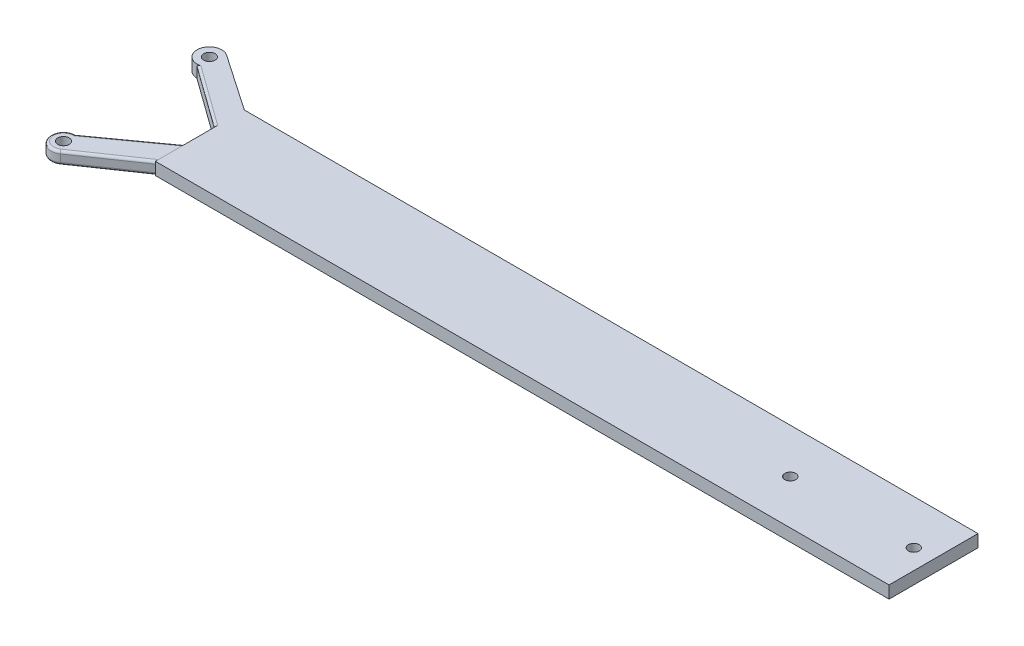
SolidWorks part; units mm, degrees
ref_plane "Płaszczyzna przednia" through (0, 0, 0) normal (0, 0, 1) x (1, 0, 0)
ref_plane "Płaszczyzna górna" through (0, 0, 0) normal (0, 1, 0) x (1, 0, 0)
ref_plane "Płaszczyzna prawa" through (0, 0, 0) normal (1, 0, 0) x (0, 0, -1)
sketch "Szkic1" plane through (0, -0.6011, 0) normal (0, -1, 0) x (1, 0, 0)
  line L11 (-159.4499, 53.1337) -> (-159.4499, 35.1337)
  line L14 (-10.9498, 35.1337) -> (-159.4499, 35.1337)
  line L15 (-10.9498, 35.1337) -> (-10.9498, 53.1337)
  line L16 (-10.9498, 53.1337) -> (-159.4499, 53.1337)
  circle A0 centre (-14.9498, 44.1337) radius 1.1 construction
  circle A1 centre (-39.9499, 44.1337) radius 1.1 construction
  circle A2 centre (-14.9498, 44.1337) radius 1.1
  circle A3 centre (-39.9499, 44.1337) radius 1.1
  dimension "D1" = 18
  dimension "D2" = 9
  dimension "D3" = 9
  dimension "D4" = 4
  dimension "D5" = 119.5
  dimension "D6" = 25.0001
extrude "Dodanie-wyciągnięcie1" add sketch "Szkic1" along normal blind 2.5
sketch "Szkic3" plane through (0, -3.1011, 0) normal (0, -1, 0) x (1, 0, 0)
  line L2 (-169.9003, 58.1452) -> (-170.1612, 57.6835)
  line L3 (-169.9187, 28.5503) -> (-170.1612, 28.0835)
  line L4 (-172.3266, 56.4033) -> (-159.4499, 47.1337)
  line L5 (-159.4499, 53.1337) -> (-159.4499, 35.1337) construction
  line L6 (-170.8688, 60.9652) -> (-159.4499, 53.1337)
  line L7 (-159.4499, 53.1337) -> (-159.4499, 47.1337)
  line L8 (-172.3266, 31.8636) -> (-159.4499, 41.1337)
  line L9 (-170.8687, 27.3018) -> (-159.4499, 35.1337)
  circle A2 centre (-172.283, 29.3637) radius 1.15
  circle A3 centre (-172.283, 58.9032) radius 1.15
  circle A4 centre (-172.283, 29.3637) radius 2.5003
  circle A5 centre (-172.283, 58.9032) radius 2.5003
  line M3 (-159.4499, 53.1337) -> (-159.4499, 35.1337)
  dimension "D1" = 6
  dimension "D2" = 6
extrude "Dodanie-wyciągnięcie2" add sketch "Szkic3" against normal blind 2.5 separate body contours A4 L9 L8 M3 | A5 L4 L6 M3 | A5 A3 | A4 A2 region at (-164.9277, -3.1011, 53.897) region at (-164.9277, -3.1011, 34.3701) region at (-174.5972, -3.1011, 59.6428) region at (-170.58, -3.1011, 31.0966)
sketch "Szkic8" plane through (0, -3.1011, 0) normal (0, -1, 0) x (1, 0, 0)
  line L1 (-159.4499, 47.1337) -> (-44.9494, 47.1337)
  line L2 (-159.4499, 47.1337) -> (-159.4499, 40.8642)
  line L3 (-159.4499, 40.8642) -> (-44.9494, 40.8642)
  line L4 (-44.9494, 47.1337) -> (-44.9494, 40.8642)
extrude "Dodanie-wyciągnięcie3" add sketch "Szkic8" along normal blind 1
fillet "Zaokrąglenie1" radius 1 4 edges at (-44.9494, -4.1011, 43.999) (-159.4499, -4.1011, 43.999) (-102.1996, -4.1011, 47.1337) (-102.1996, -4.1011, 40.8642)
fillet "Zaokrąglenie4" radius 0.5 rebuild error yes
fillet "Zaokrąglenie5" radius 0.5 6 edges at (-174.6646, -3.1011, 59.6643) (-165.1593, -3.1011, 57.0494) (-165.8882, -3.1011, 51.7685) (-174.6646, -0.6011, 59.6643) (-165.8882, -0.6011, 51.7685) (-165.1593, -0.6011, 57.0494)
fillet "Zaokrąglenie7" radius 0.5 1 edges at (-165.8882, -0.6011, 36.4987)
